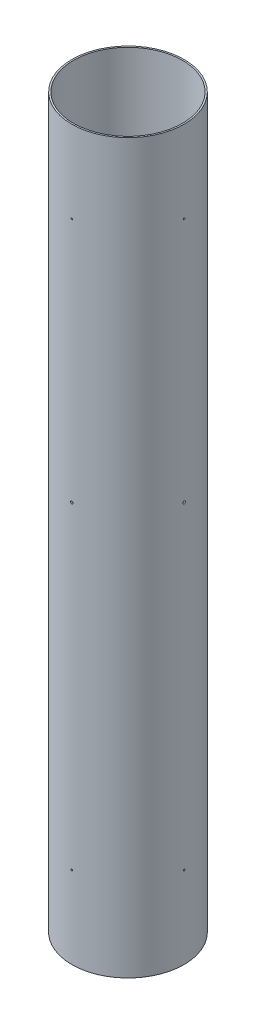
SolidWorks part; units mm, degrees
material "A-Glass Fiber"
ref_plane "Front Plane" through (0, 0, 0) normal (0, 0, 1) x (1, 0, 0)
ref_plane "Top Plane" through (0, 0, 0) normal (0, 1, 0) x (1, 0, 0)
ref_plane "Right Plane" through (0, 0, 0) normal (1, 0, 0) x (0, 0, -1)
sketch "Sketch1" plane through (0, 0, 0) normal (0, 1, 0) x (1, 0, 0)
  circle A0 centre (0, 0) radius 76.1746
  circle A1 centre (0, 0) radius 78.359
  dimension "D1" = 156.718
  dimension "D2" = 152.3492
extrude "Boss-Extrude1" add sketch "Sketch1" along normal blind 1016
ref_axis "Axis1" through (0, 1016, 0) along (0, -1, 0)
sketch "Sketch3" plane through (0, 0, 0) normal (0, 0, 1) x (1, 0, 0)
  line L0 (0, 558.8) -> (0, 1016) construction
  line L1 (78.359, 1016) -> (-78.359, 1016) construction
  line L2 (0, 0) -> (0, 114.3) construction
  circle A0 centre (0, 558.8) radius 1.75
  circle A1 centre (0, 114.3) radius 1.0922
  circle A2 centre (0, 901.7) radius 1.0922
  dimension "D2" = 3.5
  dimension "D3" = 2.1844
  dimension "D4" = 2.1844
  dimension "D1" = 457.2
  dimension "D5" = 114.3
extrude "Cut-Extrude1" cut sketch "Sketch3" against normal through all
pattern_circular "CirPattern1" count 4 over 360 about axis through (0, 1016, 0) along (0, -1, 0) of "Cut-Extrude1"
equation "\"Fwd_Tube_Length\"= 40in"
equation "\"D1@Boss-Extrude1\" = \"Fwd_Tube_Length\""
equation "\"BKHD_Screw_Diam\"= 3.5mm"
equation "\"Fwd_BKHD_From_Top\"= 18in"
equation "\"D2@Sketch3\"=\"BKHD_Screw_Diam\""
equation "\"D1@Sketch3\"=\"Fwd_BKHD_From_Top\""
equation "\"Bodytube_OD\"= 6.17in"
equation "\"Bodytube_ID\"= 5.998in"
equation "\"D2@Sketch1\"=\"Bodytube_ID\""
equation "\"D1@Sketch1\"=\"Bodytube_OD\""
equation "\"Shear_Screw_Diameter\"= 0.086in"
equation "\"D3@Sketch3\"=\"Shear_Screw_Diameter\""
equation "\"D4@Sketch3\"=\"Shear_Screw_Diameter\""
equation "\"Shear_Screw_Coupler_Location\"= 4.5in"
equation "\"D5@Sketch3\"=\"Shear_Screw_Coupler_Location\""
